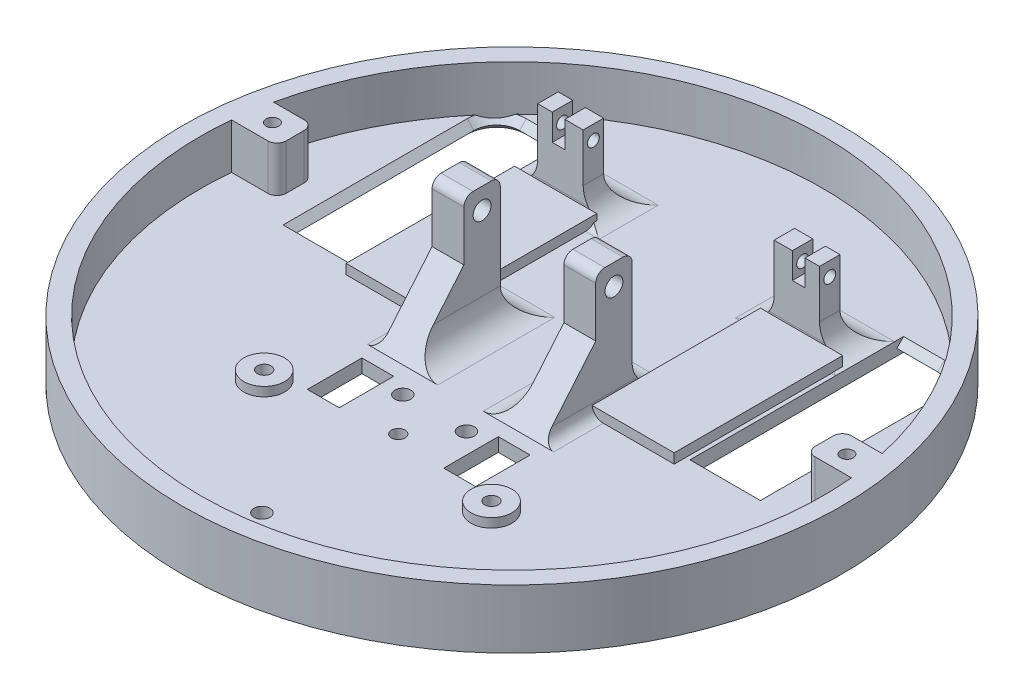
SolidWorks part; units mm, degrees
material "ABS"
ref_plane "Front Plane" through (0, 0, 0) normal (0, 0, 1) x (1, 0, 0)
ref_plane "Top Plane" through (0, 0, 0) normal (0, 1, 0) x (1, 0, 0)
ref_plane "Right Plane" through (0, 0, 0) normal (1, 0, 0) x (0, 0, -1)
sketch "Sketch2" plane through (0, 0, 0) normal (0, 1, 0) x (1, 0, 0)
  line L0 (0, 72.5) -> (0, -72.5) construction
  line L1 (-72.5, 0) -> (72.5, 0) construction
  circle A0 centre (0, 0) radius 72.5
  dimension "D1" = 145
extrude "Boss-Extrude1" add sketch "Sketch2" along normal blind 3
sketch "Sketch3" plane through (0, 3, 0) normal (0, 1, 0) x (1, 0, 0)
  line L0 (-72.5, 0) -> (72.5, 0) construction
  line L1 (-51, 47.6585) -> (-37, 47.6585)
  line L2 (-51, 47.6585) -> (-51, 2.1585)
  line L3 (-51, 2.1585) -> (-37, 2.1585)
  line L4 (-37, 47.6585) -> (-37, 2.1585)
  line L5 (0, 72.5) -> (0, -72.5) construction
  line L6 (37, 47.6585) -> (37, 2.1585)
  line L7 (51, 2.1585) -> (37, 2.1585)
  line L8 (51, 47.6585) -> (51, 2.1585)
  line L9 (51, 47.6585) -> (37, 47.6585)
  line L10 (-37, 47.6585) -> (-37, 20.3272) construction
  line L11 (0, 0) -> (0, 28.896) construction
  line L13 (0, 20.3272) -> (0, 72.5) construction
  circle A0 centre (0, 0) radius 72.5 construction
  circle A1 centre (0, 28.896) radius 6.68 construction
  point P17 (50, 0)
  dimension "D5" = 37
  dimension "D3" = 13.36
  dimension "D1" = 14
  dimension "D2" = 45.5
  dimension "D4" = 28.896
  dimension "D6" = 2.1585
extrude "Cut-Extrude1" cut sketch "Sketch3" against normal blind 5
fillet "Fillet1" radius 5 2 edges at (51, 1.5, -47.6585) (-51, 1.5, -47.6585)
sketch "Sketch4" plane through (0, 3, 0) normal (0, 1, 0) x (1, 0, 0)
  line L0 (0, 0) -> (0, 72.5) construction
  circle A0 centre (0, 0) radius 68.5
  circle A1 centre (0, 0) radius 72.5 construction
  circle A2 centre (0, 0) radius 72.5
  dimension "D1" = 4
extrude "Boss-Extrude2" add sketch "Sketch4" along normal blind 10
ref_plane "Plane1" through (0, 0, 72.5) normal (0, 0, 1) x (1, 0, 0)
sketch "草图5" plane through (0, 0, 0) normal (0, 1, 0) x (1, 0, 0)
  line L0 (21, 41.1715) -> (31, 41.1715)
  line L1 (0, 0) -> (0, 72.5) construction
  line L2 (31, 36.6715) -> (31, 41.1715)
  line L3 (21, 36.6715) -> (31, 36.6715)
  line L5 (21, 36.6715) -> (21, 41.1715)
  line L16 (0, 36.6715) -> (-21, 36.6715) construction
  line L18 (-21, 36.6715) -> (-31, 36.6715)
  line L19 (-21, 36.6715) -> (-21, 41.1715)
  line L20 (-21, 41.1715) -> (-31, 41.1715)
  line L21 (-31, 36.6715) -> (-31, 41.1715)
  circle A0 centre (0, 0) radius 72.5 construction
  dimension "D1" = 21
  dimension "D2" = 10
  dimension "D3" = 36.6715
  dimension "D4" = 4.5
extrude "凸台-拉伸2" add sketch "草图5" along normal blind 19.6
sketch "草图13" plane through (0, 0, 0) normal (0, 1, 0) x (1, 0, 0)
  line L0 (-37, 2.1585) -> (-37, -3.8875) construction
  line L1 (-37, 2.1585) -> (-23, 2.1585) construction
  line L2 (37, 2.1585) -> (18, 2.1585) construction
  line L3 (37, 2.1585) -> (37, -3.8875) construction
  line L4 (-37, -3.8875) -> (-23, -3.8875) construction
  line L5 (37, -3.8875) -> (18, -3.8875) construction
  line L6 (18, -3.8875) -> (18, 2.1585) construction
  line L7 (-23, 2.1585) -> (-23, -3.8875) construction
  line L8 (-37, 2.1585) -> (-37, 6.7325) construction
  line L9 (-9.305, 0.4303) -> (37, 0.4303) construction
  line L10 (18, 4.4303) -> (-18, 4.4303) construction
  line L11 (11, 8.4303) -> (18, 8.4303)
  line L12 (11, 8.4303) -> (11, 0.4303)
  line L13 (37, 47.6585) -> (37, 2.1585) construction
  line L14 (-11, 8.4303) -> (37, 8.4303) construction
  line L15 (0, 0) -> (0, 4.4303) construction
  line L17 (-37, 2.1585) -> (-37, 47.6585) construction
  line L18 (11, 0.4303) -> (18, 0.4303)
  line L19 (-18, 8.4303) -> (-11, 8.4303)
  line L20 (-18, 8.4303) -> (-18, 0.4303)
  line L21 (-18, 0.4303) -> (-11, 0.4303)
  line L22 (-11, 8.4303) -> (-11, 0.4303)
  line L23 (18, 8.4303) -> (18, 0.4303)
  point P28 (0, 0)
  dimension "D1" = 4.4303
  dimension "D2" = 8
  dimension "D3" = 11
  dimension "D4" = 7
extrude "凸台-拉伸4" add sketch "草图13" along normal blind 30
sketch "草图15" plane through (0, 0, 0) normal (1, 0, 0) x (0, 0, -1)
  line L0 (38.9215, 19.6) -> (38.9215, 16.48) construction
  line L1 (41.1715, 19.6) -> (36.6715, 19.6) construction
  circle A0 centre (38.9215, 16.48) radius 1.3
sketch "草图17" plane through (0, 0, 0) normal (1, 0, 0) x (0, 0, -1)
  line L0 (4.4303, 30) -> (4.4303, 25.39) construction
  line L1 (8.4303, 30) -> (0.4303, 30) construction
  circle A0 centre (4.4303, 25.39) radius 1.9685
extrude "切除-拉伸12" cut sketch "草图17" against normal blind 40 and the other way blind 40
extrude "切除-拉伸13" cut sketch "草图15" against normal blind 40 and the other way blind 40
sketch "Sketch5" plane through (0, 3, 0) normal (0, 1, 0) x (1, 0, 0)
  line L0 (0, 0) -> (0, -69.1541) construction
  line L1 (103.8296, 0) -> (-111.3937, 0) construction
  line L2 (-25, -29.5) -> (25, -29.5) construction
  circle A0 centre (0, 0) radius 68.5 construction
  circle A1 centre (-25, -29.5) radius 1.5
  circle A2 centre (25, -29.5) radius 1.5
  point P5 (0, 0)
  point P9 (0, -68.5)
  point P10 (0, -68.5)
  point P11 (0, -68.5)
  point P16 (0, -29.5)
  dimension "D1" = 3
  dimension "D2" = 25
  dimension "D3" = 39
extrude "Cut-Extrude2" cut sketch "Sketch5" against normal through all
sketch "Sketch7" plane through (0, 3, 0) normal (0, 1, 0) x (1, 0, 0)
  line L0 (0, 0) -> (0, 68.5) construction
  circle A0 centre (-25, -29.5) radius 4.5
  circle A1 centre (-25, -29.5) radius 1.5
  circle A2 centre (-25, -29.5) radius 1.5 construction
  circle A3 centre (0, 0) radius 68.5 construction
  circle A4 centre (25, -29.5) radius 1.5
  circle A5 centre (25, -29.5) radius 4.5
  dimension "D1" = 3
extrude "Boss-Extrude3" add sketch "Sketch7" along normal blind 2
sketch "Sketch8" plane through (0, 3, 0) normal (0, 1, 0) x (1, 0, 0)
  line L0 (0, 0) -> (0, -66.9892) construction
  circle A0 centre (0, -55) radius 5 construction
  circle A1 centre (0, -55) radius 1.75
  point P3 (0, -55)
  dimension "D1" = 10
  dimension "D3" = 3.5
  dimension "D2" = 55
extrude "Cut-Extrude4" cut sketch "Sketch8" against normal blind 10
sketch "Sketch9" plane through (0, 3, 0) normal (0, 1, 0) x (1, 0, 0)
  line L0 (0, 0) -> (0, -63.312) construction
  circle A0 centre (0, -25) radius 1.5
  dimension "D1" = 3
  dimension "D2" = 25
extrude "Cut-Extrude5" cut sketch "Sketch9" against normal blind 10
sketch "Sketch10" plane through (0, 0, 0) normal (0, -1, 0) x (1, 0, 0)
  line L0 (0, 55) -> (0, 0) construction
  line L1 (18.5, 26.5) -> (11.5, 26.5)
  line L2 (18.5, 26.5) -> (18.5, 14.5)
  line L3 (18.5, 14.5) -> (11.5, 14.5)
  line L4 (11.5, 26.5) -> (11.5, 14.5)
  line L5 (-11.5, 26.5) -> (-11.5, 14.5)
  line L6 (-18.5, 14.5) -> (-11.5, 14.5)
  line L7 (-18.5, 26.5) -> (-18.5, 14.5)
  line L8 (-18.5, 26.5) -> (-11.5, 26.5)
  line L9 (-15, 26.5) -> (-15, 14.5) construction
  line L10 (15, 26.5) -> (15, 14.5) construction
  dimension "D1" = 14.5
  dimension "D2" = 7
  dimension "D3" = 12
  dimension "D4" = 30
extrude "Cut-Extrude6" cut sketch "Sketch10" against normal blind 10
sketch "Sketch11" plane through (0, 3, 0) normal (0, 1, 0) x (1, 0, 0)
  line L0 (0, 0) -> (0, -25) construction
  circle A0 centre (7, -17) radius 1.75
  circle A1 centre (-7, -17) radius 1.75
  dimension "D1" = 3.5
extrude "Cut-Extrude7" cut sketch "Sketch11" against normal blind 10
sketch "Sketch12" plane through (0, 3, 0) normal (0, 1, 0) x (1, 0, 0)
  line L0 (66.9477, 14.5) -> (-66.9477, 14.5) construction
  line L1 (66.9477, 14.5) -> (58.1909, 14.5)
  line L2 (58.1909, 14.5) -> (58.1909, 6.5)
  line L3 (58.1909, 6.5) -> (68.1909, 6.5)
  line L4 (0, 0) -> (0, 14.5) construction
  line L5 (-58.1909, 6.5) -> (-68.1909, 6.5)
  line L6 (-58.1909, 14.5) -> (-58.1909, 6.5)
  line L7 (-66.9477, 14.5) -> (-58.1909, 14.5)
  line L8 (63.1909, 6.5) -> (63.1909, 14.5) construction
  circle A0 centre (0, 0) radius 68.5 construction
  arc A1 (68.1909, 6.5) -> (66.9477, 14.5) centre (0, 0) ccw
  arc A2 (-68.1909, 6.5) -> (-66.9477, 14.5) centre (0, 0) cw
  circle A3 centre (63.1909, 10.5) radius 1.4
  circle A4 centre (-63.1909, 10.5) radius 1.4
  dimension "D2" = 8
  dimension "D4" = 2.8
  dimension "D1" = 15
  dimension "D3" = 10
extrude "Boss-Extrude4" add sketch "Sketch12" along normal up to surface (10 mm away) up to face at (0, 13, 72.5)
extrude "Cut-Extrude8" cut sketch "Sketch12<2>" against normal blind 10 contours A3 | A4 region at (63.1909, 3, -10.5) region at (-63.1909, 3, -10.5)
sketch "Sketch12<2>" plane through (0, 3, 0) normal (0, 1, 0) x (1, 0, 0) same geometry as "Sketch12"
sketch "Sketch13" plane through (0, 0, -41.1715) normal (0, 0, -1) x (-1, 0, 0)
  line L0 (-27.8, 19.6) -> (-27.8, 13.92)
  line L1 (-31, 19.6) -> (-21, 19.6) construction
  line L2 (-27.8, 19.6) -> (-25.02, 19.6)
  line L3 (-25.02, 19.6) -> (-27.8, 19.6) construction
  line L4 (-25.02, 13.92) -> (-27.8, 13.92)
  line L5 (25.02, 19.6) -> (0, 19.6) construction
  line L6 (0, 36.5763) -> (0, -10.9159) construction
  line L7 (-21, 19.6) -> (-21, 3) construction
  line L8 (21, 19.6) -> (21, 3) construction
  line L9 (-25.02, 19.6) -> (0, 19.6) construction
  line L10 (-25.02, 13.92) -> (-25.02, 19.6)
  line L11 (31, 19.6) -> (27.8, 19.6) construction
  line L12 (21, 19.6) -> (31, 19.6) construction
  line L13 (27.8, 19.6) -> (27.8, 13.8192)
  line L14 (27.8, 13.8192) -> (25.02, 13.8192)
  line L15 (25.02, 13.8192) -> (25.02, 19.6)
  line L16 (25.02, 19.6) -> (27.8, 19.6)
  line L17 (-27.8, 19.6) -> (0, 19.6) construction
  dimension "D1" = 25.02
  dimension "D2" = 25.02
  dimension "D3" = 27.8
ref_plane "Plane2" through (21, 3, -41.1715) normal (1, 0, 0) x (0, 0, -1)
fillet "Fillet2" radius 6 10 edges at (-14.5, 3, -8.4303) (-11, 3, -4.4303) (11, 3, -4.4303) (14.5, 3, -8.4303) (-31, 3, -38.9215) (-26, 3, -41.1715) (-21, 3, -38.9215) (31, 3, -38.9215) (21, 3, -38.9215) (26, 3, -41.1715)
fillet "Fillet3" radius 2 4 edges at (-14.5, 30, -0.4303) (-14.5, 30, -8.4303) (14.5, 30, -0.4303) (14.5, 30, -8.4303)
fillet "Fillet4" radius 2 4 edges at (-58.1909, 8, -6.5) (-58.1909, 8, -14.5) (58.1909, 8, -6.5) (58.1909, 8, -14.5)
sketch "Sketch15" plane through (0, 3, 0) normal (0, 1, 0) x (1, 0, 0)
  line L0 (0, 48) -> (0, 0) construction
  line L1 (-20, 48) -> (20, 48)
  line L2 (-20, 48) -> (-20, 42)
  line L3 (-20, 42) -> (20, 42)
  line L4 (20, 48) -> (20, 42)
  line L5 (-20, 42) -> (-20, 40)
  line L6 (-20, 40) -> (-18.5, 40)
  line L7 (-18.5, 40) -> (-18.5, 42)
  line L8 (18.5, 40) -> (18.5, 42)
  line L9 (20, 40) -> (18.5, 40)
  line L10 (20, 42) -> (20, 40)
  point P4 (0, 0)
  point P5 (0, 48)
  dimension "D1" = 42
  dimension "D2" = 6
  dimension "D3" = 40
  dimension "D4" = 1.5
  dimension "D5" = 2
sketch "Sketch18" plane through (0, 3, 0) normal (0, 1, 0) x (1, 0, 0)
  line L0 (68.5, 0) -> (-68.5, 0) construction
  line L1 (0, 74.5) -> (0, 0) construction
  arc A0 (-68.1909, 6.5) -> (68.1909, 6.5) centre (0, 0) ccw construction
  point P5 (0, 0)
chamfer "倒角2" distance 1.5 angle 45 12 edges at (-51, 0, -22.4085) (-49.5355, 0, -46.1941) (-41.5, 0, -47.6585) (51, 3, -22.4085) (49.5355, 3, -46.1941) (41.5, 3, -47.6585) (-51, 3, -22.4085) (-49.5355, 3, -46.1941) (-41.5, 3, -47.6585) (51, 0, -22.4085) (49.5355, 0, -46.1941) (41.5, 0, -47.6585)
extrude "切除-拉伸14" cut sketch "Sketch13" against normal blind 6
chamfer "倒角3" distance 14 angle 40 2 edges at (11.5, 3, -0.4303) (-11.5, 3, -0.4303) first distance on face at (12.8485, 13.9515, -0.4303) first distance on face at (-12.8485, 13.9515, -0.4303)
fillet "圆角3" radius 2.5 4 edges at (-18, 3, -1.5566) (18, 3, -1.5566) (26, 3, -36.6715) (-26, 3, -36.6715)
sketch "草图19" plane through (0, 3, 0) normal (0, 1, 0) x (1, 0, 0)
  line L2 (36.0867, 36.6715) -> (36.0867, -0.3944) construction
  line L3 (36.0867, -0.3944) -> (18, -0.3944) construction
  line L4 (18, 0.4303) -> (18, -9.2193) construction
  line L6 (36.0867, -0.3944) -> (18, -0.3944)
  line L7 (36.0867, -0.3944) -> (36.0867, 36.6715)
  line L8 (36.0867, 36.6715) -> (18, 36.6715)
  line L9 (18, -0.3944) -> (18, 36.6715)
  line L10 (19.8734, 36.6715) -> (32.1266, 36.6715) construction
  line L11 (0, -0.3944) -> (0, 35.576) construction
  line L12 (-36.0867, -0.3944) -> (-18, -0.3944) construction
  line L13 (-36.0867, 36.6715) -> (-36.0867, -0.3944) construction
  line L14 (-18, -0.3944) -> (-18, 36.6715)
  line L15 (-36.0867, 36.6715) -> (-18, 36.6715)
  line L16 (-36.0867, -0.3944) -> (-36.0867, 36.6715)
  line L17 (-36.0867, -0.3944) -> (-18, -0.3944)
  circle A1 centre (0, 28.896) radius 6.68 construction
  point P8 (36.0867, 36.6715)
  dimension "D1" = 37.0659
  dimension "D2" = 18.0867
extrude "凸台-拉伸6" add sketch "草图19" along normal blind 2.16
extrude "凸台-拉伸8" [suppressed] add sketch "Sketch15" along normal blind 45 contours L0 L1 L2 L3 | L1 L0 L3 L4 | L6 L7 L3 L5 | L10 L3 L8 L9
ref_plane "基准面1" [suppressed] through (0, 0, -42) normal (0, 0, 1) x (1, 0, 0)
sketch "草图20" [suppressed] plane through (0, 0, -42) normal (0, 0, 1) x (1, 0, 0)
  line L0 (0, 0) -> (0, 62.4108) construction
  line L1 (0, 3) -> (-7.5, 3) construction
  line L2 (-15, 3) -> (15, 3) construction
  line L3 (-7.5, 3) -> (-7.5, 57.2613)
  line L4 (-7.5, 57.2613) -> (7.5, 57.2613)
  line L5 (7.5, 3) -> (7.5, 57.2613)
  line L11 (-7.5, 3) -> (7.5, 3)
  point P13 (0, 3)
extrude "切除-拉伸15" [suppressed] cut sketch "草图20" against normal blind 20
fillet "圆角6" [suppressed] radius 5
sketch "草图21" [suppressed] plane through (0, 0, -42) normal (0, 0, 1) x (1, 0, 0)
  line L0 (0, 0.167) -> (0, 79.2312) construction
  line L1 (0, 0) -> (0, 39) construction
  line L2 (0, 39) -> (11.5, 39) construction
  circle A0 centre (11.5, 39) radius 2
  circle A1 centre (-11.5, 39) radius 2
  point P7 (0, 39)
  point P8 (11.5, 39)
  dimension "D1" = 90
  dimension "D2" = 11.5
extrude "切除-拉伸16" [suppressed] cut sketch "草图21" against normal blind 20
fillet "圆角7" [suppressed] radius 3
